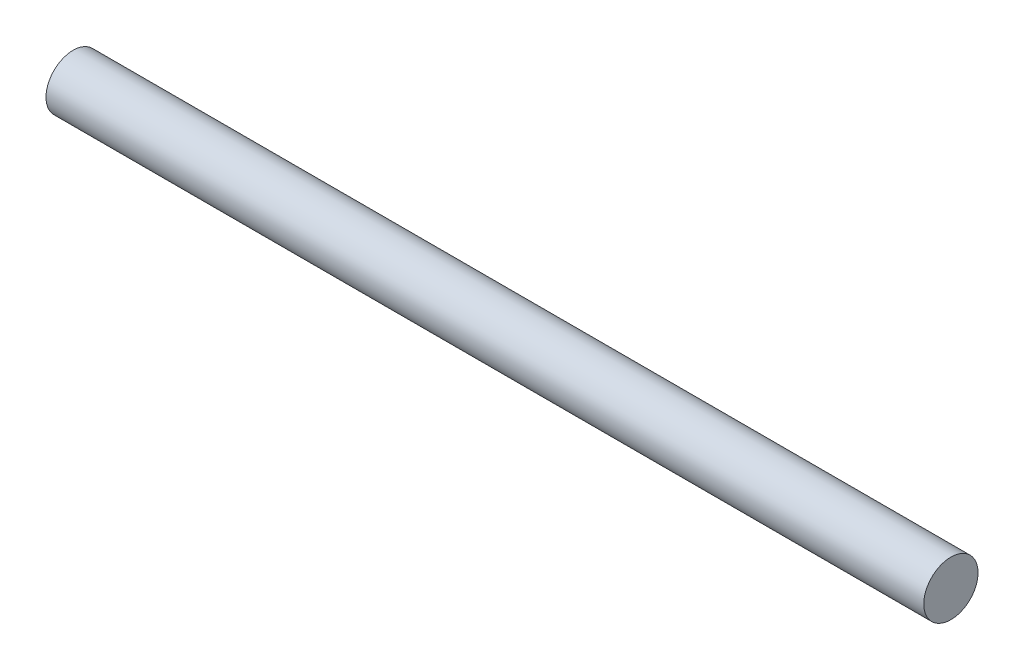
SolidWorks part; units mm, degrees
material "Brass"
ref_plane "Front" through (0, 0, 0) normal (0, 0, 1) x (1, 0, 0)
ref_plane "Top" through (0, 0, 0) normal (0, 1, 0) x (1, 0, 0)
ref_plane "Right" through (0, 0, 0) normal (1, 0, 0) x (0, 0, -1)
sketch "Sketch1" plane through (0, 0, 0) normal (1, 0, 0) x (0, 0, -1)
  circle A0 centre (0, 0) radius 1.5
  dimension "D1" = 3
extrude "Boss-Extrude1" add sketch "Sketch1" along normal mid plane 48.5
